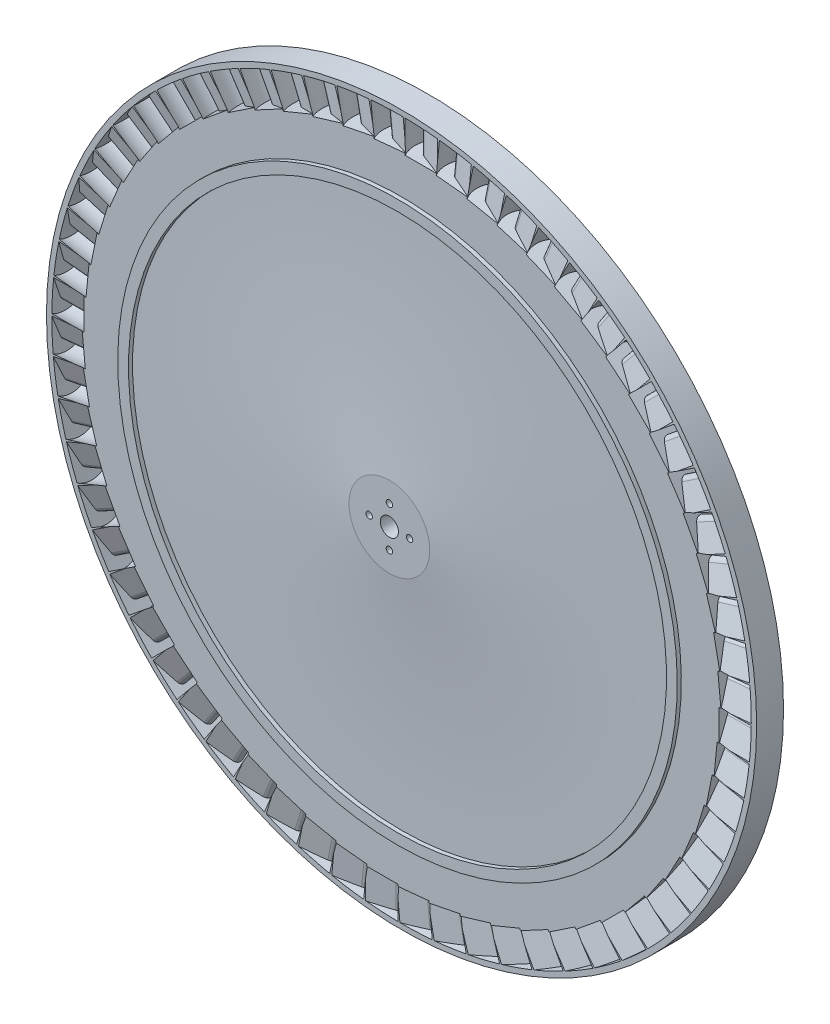
SolidWorks part; units mm, degrees
material "Nickel"
ref_plane "Front Plane" through (0, 0, 0) normal (1, 0, 0) x (0, 1, 0)
ref_plane "Top Plane" through (0, 0, 0) normal (0, 0, 1) x (0, 1, 0)
ref_plane "Right Plane" through (0, 0, 0) normal (0, 1, 0) x (-1, 0, 0)
sketch "Sketch1" plane through (0, 0, 0) normal (1, 0, 0) x (0, 1, 0)
  line L0 (0, 0) -> (-130, 0) construction
  line L1 (-130, 5) -> (-130, -5)
  line L2 (-130, -5) -> (-100, -5)
  line L3 (-130, 5) -> (-100, 5)
  line L4 (-15, 9.525) -> (0, 9.525)
  line L5 (0, 9.525) -> (0, -9.525)
  line L6 (0, -9.525) -> (-15, -9.525)
  line L7 (-100, -5) -> (-100, -6.5)
  line L8 (-100, -6.5) -> (-104, -6.5)
  line L9 (-104, -6.5) -> (-104, -5)
  line L10 (-100, 5) -> (-100, 6.5)
  line L11 (-100, 6.5) -> (-104, 6.5)
  line L12 (-104, 6.5) -> (-104, 5)
  line L13 (-130, 5) -> (-132, 5)
  line L14 (-132, 5) -> (-132, -5)
  line L15 (-132, -5) -> (-130, -5)
  arc A0 (-100, 5) -> (-15, 9.525) centre (-100, 805.605) ccw
  arc A1 (-100, -5) -> (-15, -9.525) centre (-100, -805.605) cw
  dimension "D1" = 132
  dimension "D2" = 10
  dimension "D3" = 30
  dimension "D4" = 19.05
  dimension "D5" = 15
  dimension "D6" = 1.5
  dimension "D7" = 4
  dimension "D8" = 2
revolve "Revolve1" add sketch "Sketch1" angle 360 about L5 region at (0, -56.0322, -3.466) region at (0, -56.0322, 3.466) region at (0, -102, 5.75) region at (0, -102, -5.75)
sketch "Sketch2" plane through (0, 0, 0) normal (0, 0, 1) x (0, 1, 0)
  line L0 (0, 7.5) -> (0, -7.5) construction
  line L1 (-7.5, 0) -> (7.5, 0) construction
  circle A0 centre (0, 7.5) radius 1.1906
  circle A1 centre (-7.5, 0) radius 1.1906
  circle A2 centre (0, -7.5) radius 1.1906
  circle A3 centre (7.5, 0) radius 1.1906
  circle A4 centre (0, 0) radius 3.3782
  dimension "D1" = 2.3812
  dimension "D3" = 6.7564
  dimension "D2" = 15
extrude "Cut-Extrude1" cut sketch "Sketch2" against normal through all both and the other way through all contours A1 | A0 | A3 | A2 | A4
ref_plane "Plane1" through (130, 0, 0) normal (1, 0, 0) x (0, 1, 0)
sketch "Sketch4" plane through (130, 0, 0) normal (1, 0, 0) x (0, 1, 0)
  line L0 (-104, -5) -> (104, -5) construction
  line L1 (130, 5) -> (-130, 5) construction
  line L2 (-1.3397, 5) -> (4.4338, -5) construction
  line L3 (-1.3397, 5) -> (-13.3397, 5)
  line L4 (-13.3397, 5) -> (-5.2752, 1.864)
  line L5 (-5.2752, -1.864) -> (-13.3397, -5)
  line L6 (-13.3397, -5) -> (-1.3397, -5)
  line L7 (-4, 0) -> (0, 0) construction
  arc A0 (-1.3397, 5) -> (-1.3397, -5) centre (-10, 0) cw
  arc A1 (-5.2752, 1.864) -> (-5.2752, -1.864) centre (-6, 0) cw
  arc A2 (-13.3397, 5) -> (-13.3397, -5) centre (-22, 0) cw
  point P18 (-12, 0)
  dimension "D1" = 60
  dimension "D2" = 2
  dimension "D3" = 4
  dimension "D4" = 12
extrude "Cut-Extrude2" cut sketch "Sketch4" against normal blind 12 and the other way through all contours L4 A1 L5 L6 A0 L3 region at (130, -0.1667, 0)
ref_axis "Axis1" through (0, 0, 10.4775) along (0, 0, -1)
pattern_circular "CirPattern1" count 64 over 360 about axis through (0, 0, 10.4775) along (0, 0, -1) of "Cut-Extrude2"
revolve "Revolve3" add sketch "Sketch1<3>" angle 360 about axis through (0, 0, 10.4775) along (0, 0, -1) region at (0, -131, 0)
sketch "Sketch1<3>" plane through (0, 0, 0) normal (1, 0, 0) x (0, 1, 0) same geometry as "Sketch1"
